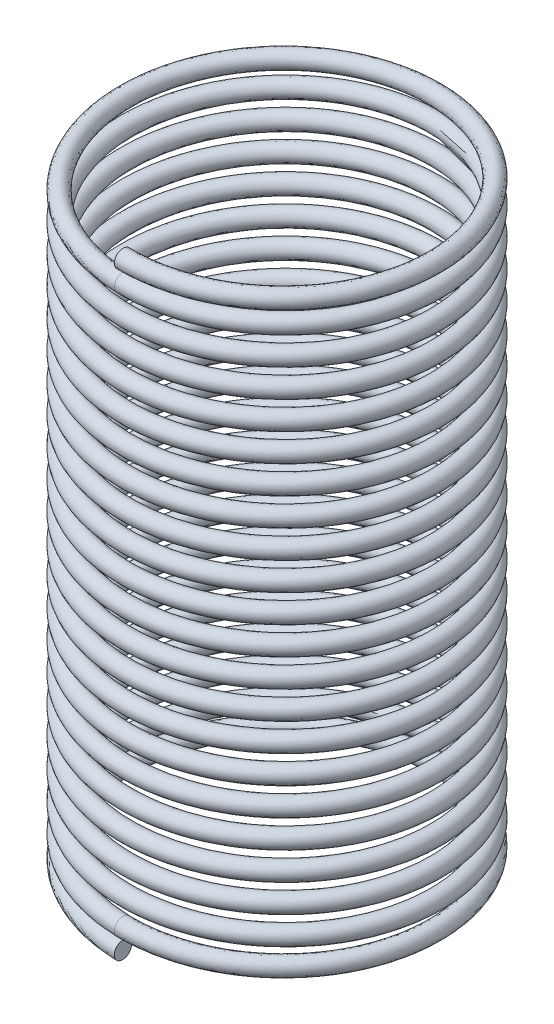
SolidWorks part; units mm, degrees
note: '?' marks a value the reader was unsure of.
ref_plane "Front Plane" through (0, 0, 0) normal (0, 0, 1) x (1, 0, 0)
ref_plane "Top Plane" through (0, 0, 0) normal (0, 1, 0) x (1, 0, 0)
ref_plane "Right Plane" through (0, 0, 0) normal (1, 0, 0) x (0, 0, -1)
sketch "Sketch3" plane through (0, 0, 0) normal (0, 1, 0) x (1, 0, 0)
  line L0 (0, 0) -> (-35.9738, 35.9738) construction
  circle A0 centre (0, 0) radius 4.5
  dimension "D1" = 9
curve "Helix/Spiral_middle" pitch 0.81 height 16.2 turns 20
sketch "Sketch5" plane through (0, 0, 0) normal (0, 1, 0) x (1, 0, 0)
  circle A0 centre (0, 0) radius 4.5
  dimension "D1" = 9
curve "Helix/Spiral_bottom" pitch 0.6 height 0.6 turns 1
ref_plane "Plane2" through (0, 16.2, 0) normal (0, 1, 0) x (1, 0, 0)
sketch "Sketch7" plane through (0, 16.2, 0) normal (0, 1, 0) x (1, 0, 0)
  circle A0 centre (0, 0) radius 4.5
  dimension "D1" = 9
curve "Helix/Spiral_top" pitch 0.6 height 0.6 turns 1
ref_plane "Plane3" through (0, 16.8, 4.5) normal (-0.9998, 0.0212, 0) x (0, 0, 1)
ref_plane "Plane4" through (0, -0.6, 4.5) normal (0.9998, -0.0212, 0) x (0, 0, -1)
sketch "Sketch9" plane through (0, -0.6, 4.5) normal (0.9998, -0.0212, 0) x (0, 0, -1)
  line L0 (0.2732, -0.2147) -> (-0.2268, -0.2147) construction
  circle A0 centre (0.0232, 0.0353) radius 0.25
  dimension "D1" = 0.5
curve "CompCurve1"
sweep "Sweep3" add profiles "Sketch9" path "CompCurve1"
sketch "TopCenterline" plane through (0, 0, 0) normal (1, 0, 0) x (0, 0, -1)
  line L0 (0, 0) -> (0, 43.2413) construction
ref_axis "Axis1" through (0, 0, 0) along (0, 1, 0)?
ref_plane "BottomPlane" through (0, -0.8146, 0) normal (0, 1, 0) x (1, 0, 0)
sketch "Sketch14" plane through (-0.3563, 0.0076, 0) normal (-0.9998, 0.0212, 0) x (0, 0, 1)
  line L0 (4.7268, 17.0815) -> (4.2268, 17.0815) construction
ref_plane "TopPlane" through (0, 17.0852, 0) normal (0, 1, 0) x (1, 0, 0)
